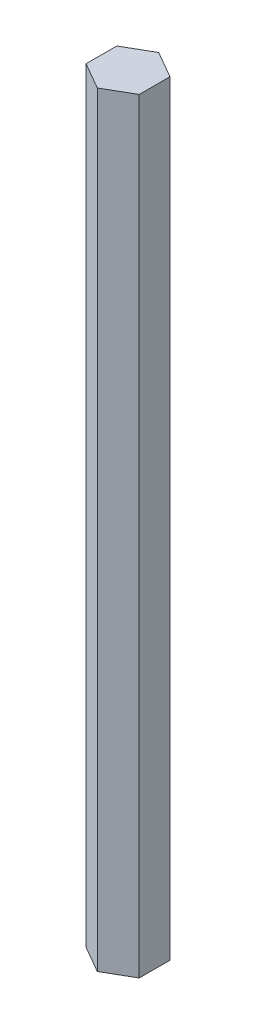
SolidWorks part; units mm, degrees
ref_plane "Front Plane" through (0, 0, 0) normal (0, 0, 1) x (1, 0, 0)
ref_plane "Top Plane" through (0, 0, 0) normal (0, 1, 0) x (1, 0, 0)
ref_plane "Right Plane" through (0, 0, 0) normal (1, 0, 0) x (0, 0, -1)
sketch "Sketch1" plane through (0, 0, 0) normal (0, 1, 0) x (1, 0, 0)
  line L0 (2, -1.8589) -> (2, 1.8589)
  line L8 (-5.2793, -3.048) -> (0, -6.096)
  line L9 (0, -6.096) -> (5.2793, -3.048)
  line L10 (5.2793, -3.048) -> (5.2793, 3.048)
  line L11 (5.2793, 3.048) -> (0, 6.096)
  line L12 (0, 6.096) -> (-5.2793, 3.048)
  line L13 (-5.2793, 3.048) -> (-5.2793, -3.048)
  arc A1 (2, 1.8589) -> (2, -1.8589) centre (0, 0) ccw
  circle A2 centre (0, 0) radius 6.096 construction
  dimension "D1" = 12.192
  dimension "D2" = 5.461
  dimension "D3" = 2
extrude "Boss-Extrude1" add sketch "Sketch1" along normal blind 151.892 contours L12 L13 L8 L9 L10 L11 A1 L0 | L0 A1
extrude "Cut-Extrude1" cut sketch "Sketch1<3>" along normal blind 10.16 contours A1 L0
sketch "Sketch1<3>" plane through (0, 0, 0) normal (0, 1, 0) x (1, 0, 0) same geometry as "Sketch1"
